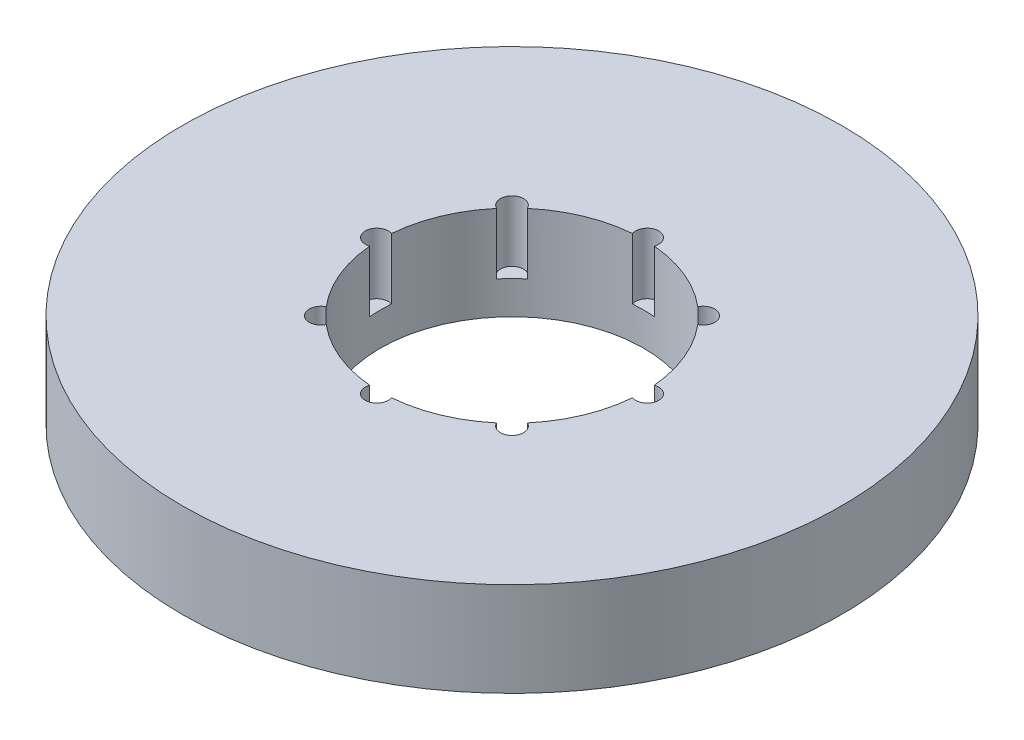
SolidWorks part; units mm, degrees
ref_plane "Front Plane" through (0, 0, 0) normal (0, 0, 1) x (1, 0, 0)
ref_plane "Top Plane" through (0, 0, 0) normal (0, 1, 0) x (1, 0, 0)
ref_plane "Right Plane" through (0, 0, 0) normal (1, 0, 0) x (0, 0, -1)
sketch "Sketch1" plane through (0, 0, 0) normal (0, 1, 0) x (1, 0, 0)
  circle A0 centre (0, 0) radius 87.5
  dimension "FLANGE_OD" = 175
extrude "Boss-Extrude1" add sketch "Sketch1" along normal blind 25
sketch "Sketch2" plane through (0, 0, 0) normal (0, 1, 0) x (1, 0, 0)
  circle A0 centre (0, 0) radius 35
  dimension "BORE_D" = 70
extrude "Cut-Extrude1" cut sketch "Sketch2" along normal through all
sketch "Sketch3" plane through (0, 25, 0) normal (0, 1, 0) x (1, 0, 0)
  circle A0 centre (0, 0) radius 35.896 construction
  circle A1 centre (-35.896, 0) radius 3.0659
  dimension "BOLT_D" = 6.1318
  dimension "BOLT_PCD" = 71.792
extrude "Cut-Extrude2" cut sketch "Sketch3" against normal blind 16.2222
pattern_circular "CirPattern1" count 8 over 360 about axis through (0, 0, 0) along (0, 1, 0) of "Cut-Extrude2"
